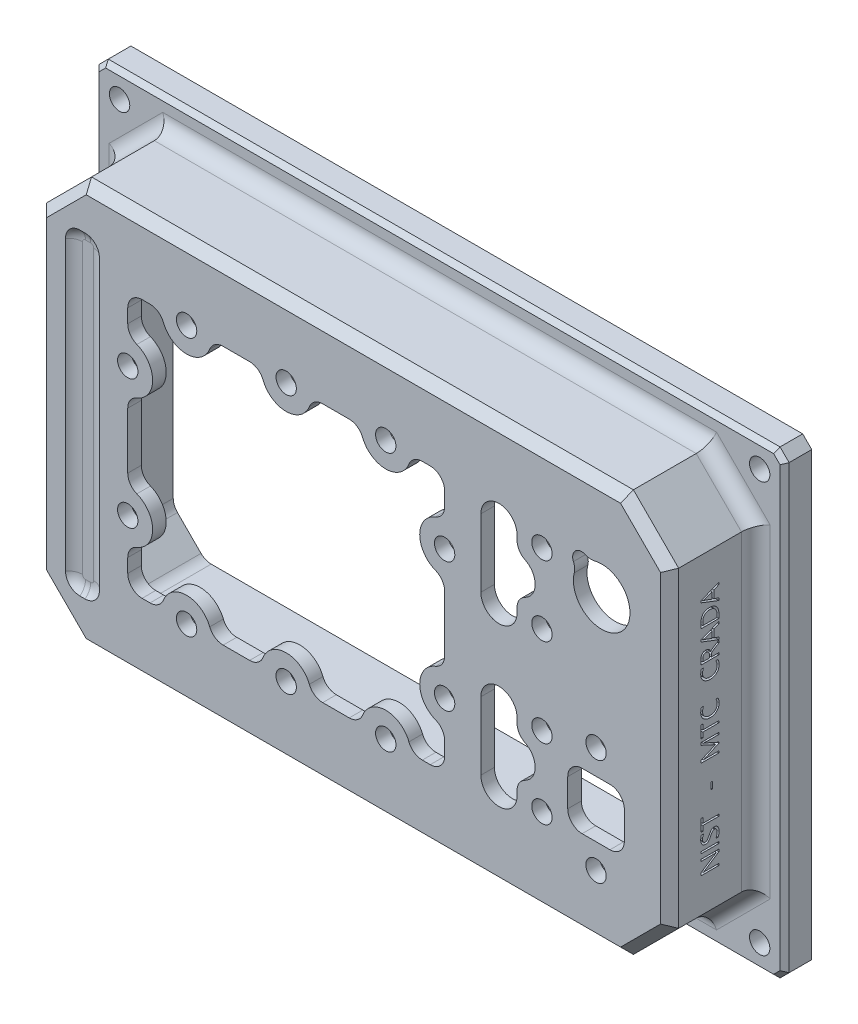
SolidWorks part; units mm, degrees
other "Title Block Table1"
other "General Table1"
other "DetailItem1"
other "DetailItem2"
other "DetailItem3"
other "DetailItem11"
material "6061 Alloy"
ref_plane "Top Plane" through (0, 0, 0) normal (0, 0, 1) x (1, 0, 0)
ref_plane "Right Plane" through (0, 0, 0) normal (0, 1, 0) x (1, 0, 0)
ref_plane "Front Plane" through (0, 0, 0) normal (1, 0, 0) x (0, 0, -1)
sketch "Sketch1" plane through (0, 0, 0) normal (0, 0, 1) x (1, 0, 0)
  line L1 (0, 0) -> (152.4, 0)
  line L2 (0, 0) -> (0, 101.6)
  line L3 (0, 101.6) -> (152.4, 101.6)
  line L4 (152.4, 0) -> (152.4, 101.6)
  dimension "D1" = 101.6
  dimension "D2" = 152.4
extrude "Flange, Base" add sketch "Sketch1" along normal blind 6
sketch "Sketch2" plane through (0, 0, 6) normal (0, 0, 1) x (1, 0, 0)
  line L4 (16.35, 95.25) -> (6.35, 85.25)
  line L5 (146.05, 85.25) -> (136.05, 95.25)
  line L6 (136.05, 6.35) -> (146.05, 16.35)
  line L7 (6.35, 16.35) -> (16.35, 6.35)
  line L8 (146.05, 6.35) -> (146.05, 95.25)
  line L9 (6.35, 6.35) -> (146.05, 6.35)
  line L10 (6.35, 95.25) -> (6.35, 6.35)
  line L11 (146.05, 95.25) -> (6.35, 95.25)
  line L12 (146.05, 16.35) -> (146.05, 85.25)
  line L13 (16.35, 6.35) -> (136.05, 6.35)
  line L14 (6.35, 85.25) -> (6.35, 16.35)
  line L15 (136.05, 95.25) -> (16.35, 95.25)
  dimension "D1" = 6.35
extrude "Cover, Exterior" add sketch "Sketch2" along normal blind 19.05
hole_wizard "4X, Clearance Hole, M4, Flange" positions "Sketch3" profile "Sketch4" hole size "M4" standard "ANSI Metric" end condition through all
sketch "Sketch3" plane through (0, 0, 6) normal (0, 0, 1) x (1, 0, 0)
  line L0 (0, 0) -> (152.4, 0) construction
  line L1 (152.4, 0) -> (152.4, 101.6) construction
  line L2 (152.4, 101.6) -> (0, 101.6) construction
  line L3 (0, 101.6) -> (0, 0) construction
  circle A0 centre (146.9, 5.5) radius 5.5 construction
  circle A1 centre (5.5, 5.5) radius 5.5 construction
  circle A2 centre (5.5, 96.1) radius 5.5 construction
  circle A3 centre (146.9, 96.1) radius 5.5 construction
  point P0 (146.9, 5.5)
  point P11 (5.5, 5.5)
  point P13 (5.5, 96.1)
  point P15 (146.9, 96.1)
  dimension "D1" = 11
  dimension "D2" = 11
  dimension "D3" = 11
  dimension "D4" = 11
sketch "Sketch4" plane through (146.9, 5.5, 6) normal (1, 0, 0) x (0, -1, 0)
  line L0 (0, 0) -> (0, 6)
  line L1 (0, 6) -> (2.25, 6)
  line L2 (2.25, 6) -> (2.25, 0)
  line L5 (2.25, 0) -> (0, 0)
  line L11 (0, -6.35) -> (0, 107.95) construction
  dimension "Thru Hole Dia." = 4.5
  dimension "Thru Hole Depth" = 6
sketch "Sketch5" plane through (0, 0, 0) normal (0, 0, -1) x (-1, 0, 0)
  line L16 (-11.35, 83.1789) -> (-18.4211, 90.25)
  line L17 (-11.35, 18.4211) -> (-11.35, 83.1789)
  line L18 (-18.4211, 11.35) -> (-11.35, 18.4211)
  line L19 (-133.9789, 11.35) -> (-18.4211, 11.35)
  line L20 (-141.05, 18.4211) -> (-133.9789, 11.35)
  line L21 (-141.05, 83.1789) -> (-141.05, 18.4211)
  line L22 (-133.9789, 90.25) -> (-141.05, 83.1789)
  line L23 (-18.4211, 90.25) -> (-133.9789, 90.25)
  line L24 (-11.35, 83.1789) -> (-18.4211, 90.25)
  line L25 (-11.35, 18.4211) -> (-11.35, 83.1789)
  line L26 (-18.4211, 11.35) -> (-11.35, 18.4211)
  line L27 (-133.9789, 11.35) -> (-18.4211, 11.35)
  line L28 (-141.05, 18.4211) -> (-133.9789, 11.35)
  line L29 (-141.05, 83.1789) -> (-141.05, 18.4211)
  line L30 (-133.9789, 90.25) -> (-141.05, 83.1789)
  line L31 (-18.4211, 90.25) -> (-133.9789, 90.25)
  dimension "D1" = 5
extrude "Cover, Interior" cut sketch "Sketch5" against normal offset from surface (22.05 mm away) 3 up to face at (76.2, 50.8, 25.05)
sketch "Sketch6" plane through (0, 0, 25.05) normal (0, 0, 1) x (1, 0, 0)
  line L0 (6.35, 50.8) -> (146.05, 50.8) construction
  line L1 (26.35, 79.375) -> (33.85, 79.375)
  line L2 (26.35, 79.375) -> (26.35, 70.5875)
  line L3 (26.35, 22.225) -> (33.85, 22.225)
  line L4 (96.35, 79.375) -> (96.35, 70.5875)
  line L5 (6.35, 85.25) -> (6.35, 16.35) construction
  line L6 (146.05, 16.35) -> (146.05, 85.25) construction
  line L7 (26.35, 31.0125) -> (26.35, 22.225)
  line L8 (26.35, 59.5875) -> (26.35, 42.0125)
  line L9 (44.85, 79.375) -> (55.85, 79.375)
  line L10 (66.85, 79.375) -> (77.85, 79.375)
  line L11 (88.85, 79.375) -> (96.35, 79.375)
  line L12 (88.85, 22.225) -> (96.35, 22.225)
  line L13 (66.85, 22.225) -> (77.85, 22.225)
  line L14 (44.85, 22.225) -> (55.85, 22.225)
  line L15 (96.35, 31.0125) -> (96.35, 22.225)
  line L16 (96.35, 59.5875) -> (96.35, 42.0125)
  arc A0 (55.85, 79.375) -> (66.85, 79.375) centre (61.35, 79.375) ccw
  arc A1 (77.85, 79.375) -> (88.85, 79.375) centre (83.35, 79.375) ccw
  arc A2 (88.85, 22.225) -> (77.85, 22.225) centre (83.35, 22.225) ccw
  arc A3 (66.85, 22.225) -> (55.85, 22.225) centre (61.35, 22.225) ccw
  arc A4 (33.85, 79.375) -> (44.85, 79.375) centre (39.35, 79.375) ccw
  arc A5 (44.85, 22.225) -> (33.85, 22.225) centre (39.35, 22.225) ccw
  arc A6 (26.35, 59.5875) -> (26.35, 70.5875) centre (26.35, 65.0875) ccw
  arc A7 (96.35, 70.5875) -> (96.35, 59.5875) centre (96.35, 65.0875) ccw
  arc A8 (96.35, 42.0125) -> (96.35, 31.0125) centre (96.35, 36.5125) ccw
  arc A9 (26.35, 31.0125) -> (26.35, 42.0125) centre (26.35, 36.5125) ccw
  dimension "D4" = 11
  dimension "D2" = 70
  dimension "D3" = 20
  dimension "D8" = 22
  dimension "D9" = 22
  dimension "D10" = 14.2875
  dimension "D13" = 28.575
  dimension "D14" = 57.15
  dimension "D15" = 35
  dimension "D5" = 2
  dimension "D6" = 2
  dimension "D7" = 2
  dimension "D11" = 2
  dimension "D12" = 2
extrude "Window, Cover" cut sketch "Sketch6" against normal through all
hole_wizard "10X, Clearance Hole, M4, Window" positions "3DSketch1" profile "Sketch7" hole size "M4" standard "ANSI Metric" end condition through all
sketch3d "3DSketch1"
  line L0 (39.35, 22.225, 22.05) -> (39.35, 22.225, 25.05) construction
  line L1 (61.35, 22.225, 22.05) -> (61.35, 22.225, 25.05) construction
  line L2 (83.35, 22.225, 22.05) -> (83.35, 22.225, 25.05) construction
  line L3 (96.35, 36.5125, 22.05) -> (96.35, 36.5125, 25.05) construction
  line L4 (96.35, 65.0875, 22.05) -> (96.35, 65.0875, 25.05) construction
  line L5 (83.35, 79.375, 22.05) -> (83.35, 79.375, 25.05) construction
  line L6 (61.35, 79.375, 22.05) -> (61.35, 79.375, 25.05) construction
  line L7 (39.35, 79.375, 22.05) -> (39.35, 79.375, 25.05) construction
  line L8 (26.35, 65.0875, 22.05) -> (26.35, 65.0875, 25.05) construction
  line L9 (26.35, 36.5125, 22.05) -> (26.35, 36.5125, 25.05) construction
  point P0 (39.35, 22.225, 25.05)
  point P4 (61.35, 22.225, 25.05)
  point P8 (83.35, 22.225, 25.05)
  point P12 (96.35, 36.5125, 25.05)
  point P16 (96.35, 65.0875, 25.05)
  point P20 (83.35, 79.375, 25.05)
  point P24 (61.35, 79.375, 25.05)
  point P28 (39.35, 79.375, 25.05)
  point P32 (26.35, 65.0875, 25.05)
  point P36 (26.35, 36.5125, 25.05)
sketch "Sketch7" plane through (39.35, 22.225, 25.05) normal (1, 0, 0) x (0, -1, 0)
  line L0 (0, 0) -> (0, 25.05)
  line L1 (0, 25.05) -> (2.25, 25.05)
  line L2 (2.25, 25.05) -> (2.25, 0)
  line L5 (2.25, 0) -> (0, 0)
  line L11 (0, -6.35) -> (0, 107.95) construction
  dimension "Thru Hole Dia." = 4.5
  dimension "Thru Hole Depth" = 25.05
sketch "Sketch8" plane through (0, 0, 25.05) normal (0, 0, 1) x (1, 0, 0)
  line L0 (12.6, 50.8) -> (6.35, 50.8) construction
  line L1 (12.6, 85.8) -> (20.1, 85.8)
  line L2 (12.6, 85.8) -> (12.6, 15.8)
  line L3 (12.6, 15.8) -> (20.1, 15.8)
  line L4 (20.1, 85.8) -> (20.1, 15.8)
  line L5 (6.35, 85.25) -> (6.35, 16.35) construction
  line L6 (6.35, 85.25) -> (6.35, 16.35) construction
  point P9 (16.35, 85.8)
  dimension "D1" = 7.5
  dimension "D2" = 70
  dimension "D3" = 10
extrude "Groove, Top, Cover" cut sketch "Sketch8" against normal blind 1.25
sketch "Sketch9" plane through (0, 0, 25.05) normal (0, 0, 1) x (1, 0, 0)
  line L0 (112.35, 29.3) -> (112.35, 25.8)
  line L1 (123.55, 38.3) -> (136.05, 38.3)
  line L2 (123.55, 38.3) -> (123.55, 25.8)
  line L3 (123.55, 25.8) -> (136.05, 25.8)
  line L4 (136.05, 38.3) -> (136.05, 25.8)
  line L5 (146.05, 16.35) -> (146.05, 85.25) construction
  line L6 (108.35, 75.8) -> (108.35, 60.8) construction
  line L7 (112.35, 75.8) -> (112.35, 72.3)
  line L8 (104.35, 75.8) -> (104.35, 60.8)
  line L9 (108.35, 40.8) -> (108.35, 25.8) construction
  line L10 (112.35, 40.8) -> (112.35, 37.3)
  line L11 (104.35, 40.8) -> (104.35, 25.8)
  line L12 (112.35, 64.3) -> (112.35, 60.8)
  line L13 (96.35, 42.0125) -> (96.35, 59.5875) construction
  line L14 (146.05, 50.8) -> (96.35, 50.8) construction
  line L15 (146.05, 16.35) -> (146.05, 85.25) construction
  line L16 (96.35, 22.225) -> (96.35, 31.0125) construction
  line L17 (131.05, 73.3) -> (126.6306, 77.7194) construction
  line L18 (131.05, 73.3) -> (124.8, 73.3) construction
  arc A0 (112.35, 75.8) -> (104.35, 75.8) centre (108.35, 75.8) ccw
  arc A1 (104.35, 60.8) -> (112.35, 60.8) centre (108.35, 60.8) ccw
  arc A2 (112.35, 40.8) -> (104.35, 40.8) centre (108.35, 40.8) ccw
  arc A3 (104.35, 25.8) -> (112.35, 25.8) centre (108.35, 25.8) ccw
  arc A4 (112.35, 64.3) -> (112.35, 72.3) centre (112.35, 68.3) ccw
  arc A5 (112.35, 29.3) -> (112.35, 37.3) centre (112.35, 33.3) ccw
  arc A7 (125.4609, 76.0971) -> (128.2529, 78.8891) centre (131.05, 73.3) ccw
  arc A8 (128.2529, 78.8891) -> (125.4609, 76.0971) centre (126.6306, 77.7194) ccw
  point P4 (146.05, 50.8)
  point P14 (108.35, 33.3)
  point P33 (108.35, 68.3)
  dimension "D5" = 4
  dimension "D6" = 8
  dimension "D10" = 12.5
  dimension "D11" = 4
  dimension "D1" = 12.5
  dimension "D2" = 12.5
  dimension "D3" = 10
  dimension "D4" = 12.5
  dimension "D7" = 15
  dimension "D8" = 20
  dimension "D9" = 8
  dimension "D12" = 15
  dimension "D13" = 22.5
  dimension "D14" = 45
extrude "Ports, Top, Cover" cut sketch "Sketch9" against normal through all
hole_wizard "2X, Clearance Hole, M4, Port, Square" positions "3DSketch2" profile "Sketch10" hole size "M4" standard "ANSI Metric" end condition through all
sketch3d "3DSketch2"
  line L0 (136.05, 38.3, 25.05) -> (123.55, 38.3, 25.05) construction
  line L1 (123.55, 25.8, 25.05) -> (136.05, 25.8, 25.05) construction
  circle A0 centre (129.8, 43.8, 25.05) radius 5.5 construction
  circle A1 centre (129.8, 20.3, 25.05) radius 5.5 construction
  point P0 (129.8, 43.8, 25.05)
  point P2 (129.8, 20.3, 25.05)
  point P7 (129.8, 43.8, 30.55)
  point P11 (129.8, 20.3, 30.55)
  point P17 (129.8, 38.3, 25.05)
  dimension "D2" = 11
  dimension "D1" = 11
sketch "Sketch10" plane through (129.8, 43.8, 25.05) normal (1, 0, 0) x (0, -1, 0)
  line L0 (0, 0) -> (0, 25.05)
  line L1 (0, 25.05) -> (2.25, 25.05)
  line L2 (2.25, 25.05) -> (2.25, 0)
  line L5 (2.25, 0) -> (0, 0)
  line L11 (0, -6.35) -> (0, 107.95) construction
  dimension "Thru Hole Dia." = 4.5
  dimension "Thru Hole Depth" = 25.05
hole_wizard "4X, Clearance Hole, M4, Port, Slots" positions "3DSketch3" profile "Sketch11" hole size "M4" standard "ANSI Metric" end condition through all
sketch3d "3DSketch3"
  line L0 (112.35, 72.3, 25.05) -> (112.35, 75.8, 25.05) construction
  line L1 (112.35, 60.8, 25.05) -> (112.35, 64.3, 25.05) construction
  line L2 (112.35, 37.3, 25.05) -> (112.35, 40.8, 25.05) construction
  line L3 (112.35, 25.8, 25.05) -> (112.35, 29.3, 25.05) construction
  circle A0 centre (117.85, 76.046, 25.05) radius 5.5 construction
  circle A1 centre (117.85, 60.554, 25.05) radius 5.5 construction
  circle A2 centre (117.85, 41.046, 25.05) radius 5.5 construction
  circle A3 centre (117.85, 25.554, 25.05) radius 5.5 construction
  arc A4 (112.35, 64.3, 25.05) -> (112.35, 72.3, 25.05) centre (112.35, 68.3, 25.05) ccw construction
  arc A5 (112.35, 29.3, 25.05) -> (112.35, 37.3, 25.05) centre (112.35, 33.3, 25.05) ccw construction
  point P0 (117.85, 76.046, 25.05)
  point P2 (117.85, 60.554, 25.05)
  point P4 (117.85, 41.046, 25.05)
  point P6 (117.85, 25.554, 25.05)
  point P11 (117.85, 76.046, 30.55)
  point P14 (117.85, 60.554, 30.55)
  point P17 (117.85, 41.046, 30.55)
  point P20 (117.85, 25.554, 30.55)
  point P25 (112.35, 68.3, 29.05)
  point P35 (112.35, 33.3, 29.05)
  dimension "D2" = 11
  dimension "D3" = 11
  dimension "D4" = 11
  dimension "D1" = 11
sketch "Sketch11" plane through (117.85, 76.046, 25.05) normal (1, 0, 0) x (0, -1, 0)
  line L0 (0, 0) -> (0, 25.05)
  line L1 (0, 25.05) -> (2.25, 25.05)
  line L2 (2.25, 25.05) -> (2.25, 0)
  line L5 (2.25, 0) -> (0, 0)
  line L11 (0, -6.35) -> (0, 107.95) construction
  dimension "Thru Hole Dia." = 4.5
  dimension "Thru Hole Depth" = 25.05
fillet "Fillet, 3.175mm, Flange" radius 3.175 8 edges at (11.35, 11.35, 6) (76.2, 6.35, 6) (141.05, 11.35, 6) (11.35, 90.25, 6) (6.35, 50.8, 6) (76.2, 95.25, 6) (141.05, 90.25, 6) (146.05, 50.8, 6)
fillet "Fillet, 3.175mm, Window" radius 3.175 24 edges at (33.85, 79.375, 23.55) (44.85, 79.375, 23.55) (55.85, 79.375, 23.55) (66.85, 79.375, 23.55) (77.85, 79.375, 23.55) (88.85, 79.375, 23.55) (96.35, 79.375, 23.55) (96.35, 70.5875, 23.55) (96.35, 59.5875, 23.55) (96.35, 42.0125, 23.55) (96.35, 31.0125, 23.55) (77.85, 22.225, 23.55) (66.85, 22.225, 23.55) (55.85, 22.225, 23.55) (44.85, 22.225, 23.55) (33.85, 22.225, 23.55) (26.35, 22.225, 23.55) (26.35, 31.0125, 23.55) (26.35, 42.0125, 23.55) (26.35, 59.5875, 23.55) (26.35, 70.5875, 23.55) (26.35, 79.375, 23.55) (88.85, 22.225, 23.55) (96.35, 22.225, 23.55)
fillet "Fillet, 3.175mm, Ports" radius 3.175 14 edges at (12.6, 15.8, 24.425) (20.1, 15.8, 24.425) (20.1, 85.8, 24.425) (12.6, 85.8, 24.425) (136.05, 25.8, 23.55) (136.05, 38.3, 23.55) (123.55, 38.3, 23.55) (112.35, 64.3, 23.55) (112.35, 72.3, 23.55) (112.35, 29.3, 23.55) (112.35, 37.3, 23.55) (125.4609, 76.0971, 23.55) (128.2529, 78.8891, 23.55) (123.55, 25.8, 23.55)
fillet "Fillet, 3.175mm, Groove" radius 3.175 8 edges at (13.5299, 84.8701, 23.8) (16.35, 85.8, 23.8) (19.1701, 84.8701, 23.8) (20.1, 50.8, 23.8) (19.1701, 16.7299, 23.8) (16.35, 15.8, 23.8) (13.5299, 16.7299, 23.8) (12.6, 50.8, 23.8)
fillet "Fillet, 3mm, Cover, Interior" radius 3.175 16 edges at (14.8855, 14.8855, 22.05) (76.2, 11.35, 22.05) (137.5145, 14.8855, 22.05) (141.05, 50.8, 22.05) (14.8855, 86.7145, 22.05) (11.35, 50.8, 22.05) (137.5145, 86.7145, 22.05) (76.2, 90.25, 22.05) (11.35, 18.4211, 11.025) (133.9789, 11.35, 11.025) (141.05, 18.4211, 11.025) (141.05, 83.1789, 11.025) (133.9789, 90.25, 11.025) (18.4211, 90.25, 11.025) (11.35, 83.1789, 11.025) (18.4211, 11.35, 11.025)
chamfer "Chamfer, 2mm" distance 2 angle 45 12 edges at (11.35, 11.35, 25.05) (6.35, 50.8, 25.05) (11.35, 90.25, 25.05) (76.2, 95.25, 25.05) (141.05, 90.25, 25.05) (146.05, 50.8, 25.05) (141.05, 11.35, 25.05) (76.2, 6.35, 25.05) (152.4, 101.6, 3) (152.4, 0, 3) (0, 0, 3) (0, 101.6, 3)
chamfer "Chamfer, 1mm" distance 1 angle 45 8 edges at (151.4, 100.6, 6) (152.4, 50.8, 6) (151.4, 1, 6) (76.2, 0, 6) (1, 1, 6) (0, 50.8, 6) (1, 100.6, 6) (76.2, 101.6, 6)
sketch "Sketch13" plane through (146.05, 0, 0) normal (1, 0, 0) x (0, 0, -1)
  line L0 (-14.175, 16.35) -> (-14.175, 85.25) construction
  line L1 (-23.05, 16.35) -> (-9.175, 16.35) construction
  line L2 (-23.05, 85.25) -> (-9.175, 85.25) construction
  line L3 (-9.175, 16.35) -> (-9.175, 85.25) construction
  text T0 "NIST  -  MTC  CRADA" font "@Arial Unicode MS" height in points 14
  dimension "D1" = 5
extrude "Engraving, Text" cut sketch "Sketch13" against normal blind 1.5
equation "\"D2@Sketch3\"=\"D1@Sketch3\""
equation "\"D3@Sketch3\"=\"D1@Sketch3\""
equation "\"D4@Sketch3\"=\"D1@Sketch3\""
equation "\"D8@Sketch6\"=\"D9@Sketch6\""
equation "\"D10@Sketch6\"=\"D14@Sketch6\"/4"
equation "\"D15@Sketch6\"=\"D2@Sketch6\"/2"
equation "\"D13@Sketch6\"=\"D14@Sketch6\"/2"
equation "\"D2@3DSketch2\"=\"D1@3DSketch2\""
equation "\"D2@3DSketch3\"=\"D1@3DSketch3\""
equation "\"D3@3DSketch3\"=\"D1@3DSketch3\""
equation "\"D4@3DSketch3\"=\"D1@3DSketch3\""
equation "\"D1@Sketch3\"=2.5*4.4mm"
